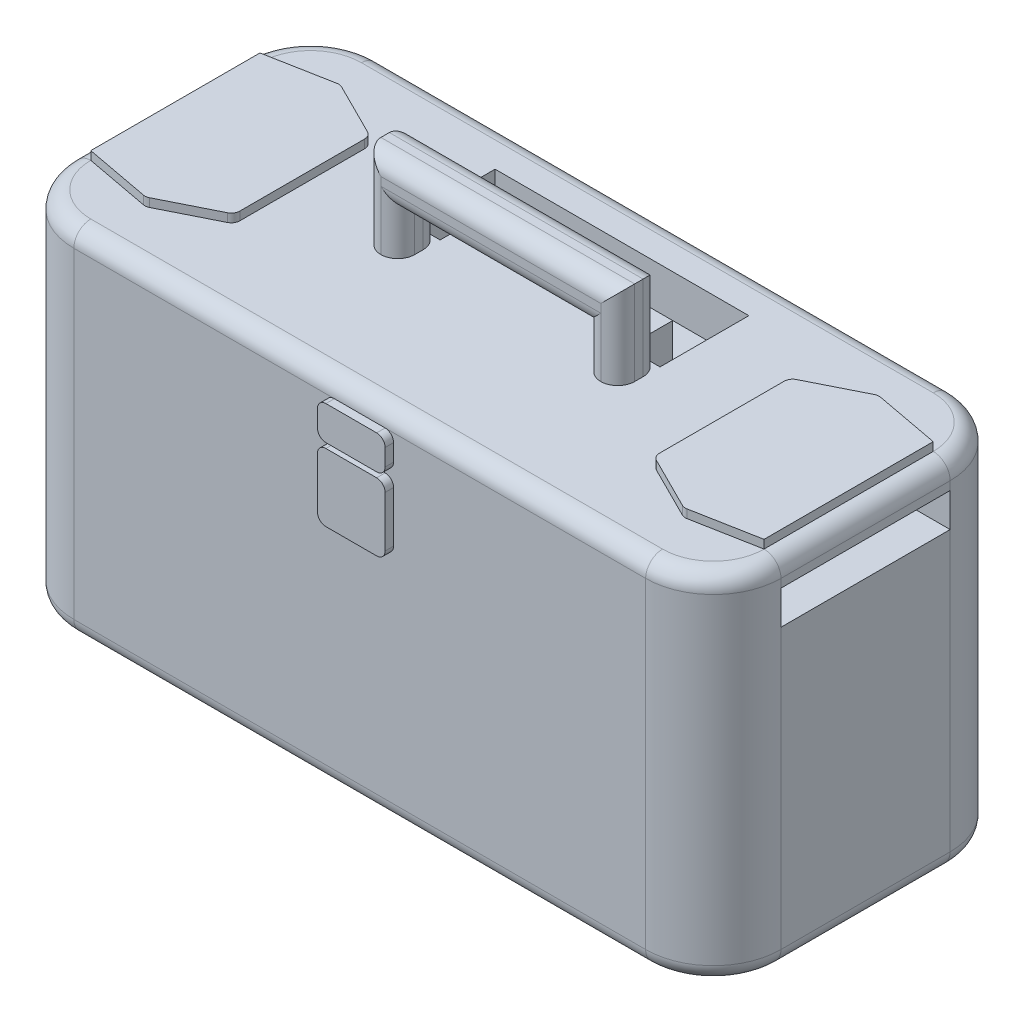
SolidWorks part; units mm, degrees
material "Kunststoff schwarz"
ref_plane "Vorne" through (0, 0, 0) normal (0, 0, 1) x (1, 0, 0)
ref_plane "Oben" through (0, 0, 0) normal (0, 1, 0) x (1, 0, 0)
ref_plane "Rechts" through (0, 0, 0) normal (1, 0, 0) x (0, 0, -1)
sketch "Skizze1" plane through (0, 0, 0) normal (0, 0, 1) x (1, 0, 0)
  line L1 (-209, 0) -> (209, 0)
  line L2 (-209, 0) -> (-209, 210)
  line L3 (-209, 210) -> (209, 210)
  line L4 (209, 0) -> (209, 210)
  point P4 (0, 0)
  dimension "D1" = 210
  dimension "D2" = 418
extrude "Aufsatz-Linear austragen1" add sketch "Skizze1" along normal mid plane 180
fillet "Verrundung1" radius 40 4 edges at (209, 105, 90) (209, 105, -90) (-209, 105, -90) (-209, 105, 90)
sketch "Skizze3" plane through (0, 210, 0) normal (0, 1, 0) x (1, 0, 0)
  line L0 (-75, -10) -> (-75, 65)
  line L1 (-75, 65) -> (75, 65)
  line L2 (75, 65) -> (75, -10)
  line L3 (75, -10) -> (55, -10)
  line L4 (55, -10) -> (55, 40)
  line L5 (55, 40) -> (-55, 40)
  line L6 (-55, 40) -> (-55, -10)
  line L7 (-55, -10) -> (-75, -10)
  line L8 (0, 90) -> (0, -90) construction
  line L9 (169, 90) -> (-169, 90) construction
  line L10 (169, -90) -> (-169, -90) construction
  dimension "D1" = 10
  dimension "D2" = 20
  dimension "D3" = 20
  dimension "D4" = 25
  dimension "D5" = 150
  dimension "D6" = 75
extrude "Schnitt-Linear austragen1" cut sketch "Skizze3" against normal blind 25
sketch "Skizze4" plane through (0, 0, 0) normal (0, 0, 1) x (1, 0, 0)
  line L0 (-75, 185) -> (-75, 260)
  line L1 (-75, 185) -> (-75, 210) construction
  line L2 (-75, 260) -> (75, 260)
  line L3 (75, 260) -> (75, 185)
  line L4 (-55, 185) -> (-55, 235)
  line L5 (-55, 235) -> (55, 235)
  line L6 (55, 235) -> (55, 185)
  line L7 (55, 185) -> (75, 185)
  line L8 (-75, 185) -> (-55, 185)
  dimension "D1" = 75
  dimension "D2" = 25
extrude "Aufsatz-Linear austragen2" add sketch "Skizze4" along normal mid plane 25
fillet "Verrundung2" radius 10 12 edges at (-75, 235, -12.5) (-55, 222.5, -12.5) (55, 222.5, -12.5) (0, 235, -12.5) (0, 260, -12.5) (75, 235, -12.5) (75, 235, 12.5) (55, 222.5, 12.5) (0, 260, 12.5) (0, 235, 12.5) (-55, 222.5, 12.5) (-75, 235, 12.5)
sketch "Skizze5" plane through (209, 0, 0) normal (1, 0, 0) x (0, 0, -1)
  line L0 (-50, 210) -> (-50, 0) construction
  line L1 (-50, 195) -> (50, 195)
  line L2 (-50, 195) -> (-50, 175)
  line L3 (-50, 175) -> (50, 175)
  line L4 (50, 195) -> (50, 175)
  line L5 (50, 0) -> (50, 210) construction
  line L6 (-50, 210) -> (50, 210) construction
  dimension "D1" = 15
  dimension "D2" = 20
extrude "Schnitt-Linear austragen2" cut sketch "Skizze5" against normal blind 20
sketch "Skizze6" plane through (-209, 0, 0) normal (-1, 0, 0) x (0, 0, 1)
  line L0 (-50, 210) -> (-50, 0) construction
  line L1 (-50, 195) -> (50, 195)
  line L2 (-50, 195) -> (-50, 175)
  line L3 (-50, 175) -> (50, 175)
  line L4 (50, 195) -> (50, 175)
  line L5 (50, 0) -> (50, 210) construction
  line L6 (50, 210) -> (-50, 210) construction
  dimension "D1" = 15
  dimension "D2" = 20
extrude "Schnitt-Linear austragen3" cut sketch "Skizze6" against normal blind 20
fillet "Verrundung4" radius 10 16 edges at (-209, 0, 0) (-197.2843, 0, 78.2843) (0, 0, 90) (197.2843, 0, 78.2843) (209, 0, 0) (197.2843, 0, -78.2843) (0, 0, -90) (197.2843, 210, -78.2843) (209, 210, 0) (197.2843, 210, 78.2843) (0, 210, 90) (-197.2843, 210, 78.2843) (-209, 210, 0) (-197.2843, 210, -78.2843) (-197.2843, 0, -78.2843) (0, 210, -90)
sketch "Skizze7" plane through (0, 210, 0) normal (0, 1, 0) x (1, 0, 0)
  line L0 (-199, 50) -> (-160.6531, 57.19)
  line L1 (-157.4956, 56.7478) -> (-126.7639, 41.382)
  line L2 (-124, 36.9098) -> (-124, -36.9098)
  line L3 (-126.7639, -41.382) -> (-157.4956, -56.7478)
  line L4 (-160.6531, -57.19) -> (-199, -50)
  line L5 (-209, 0) -> (0, 0) construction
  line L6 (-209, -50) -> (-209, 50) construction
  line L7 (-199, 50) -> (-199, -50)
  line L8 (0, 0) -> (0, 90) construction
  line L9 (-169, 90) -> (169, 90) construction
  line L10 (199, 50) -> (199, -50)
  line L11 (160.6531, -57.19) -> (199, -50)
  line L12 (126.7639, -41.382) -> (157.4956, -56.7478)
  line L13 (124, 36.9098) -> (124, -36.9098)
  line L14 (157.4956, 56.7478) -> (126.7639, 41.382)
  line L15 (199, 50) -> (160.6531, 57.19)
  arc A0 (-160.6531, -57.19) -> (-157.4956, -56.7478) centre (-159.7317, -52.2757) ccw
  arc A1 (-124, -36.9098) -> (-126.7639, -41.382) centre (-129, -36.9098) cw
  arc A2 (-124, 36.9098) -> (-126.7639, 41.382) centre (-129, 36.9098) ccw
  arc A3 (-157.4956, 56.7478) -> (-160.6531, 57.19) centre (-159.7317, 52.2757) ccw
  arc A4 (157.4956, 56.7478) -> (160.6531, 57.19) centre (159.7317, 52.2757) cw
  arc A5 (124, 36.9098) -> (126.7639, 41.382) centre (129, 36.9098) cw
  arc A6 (124, -36.9098) -> (126.7639, -41.382) centre (129, -36.9098) ccw
  arc A7 (160.6531, -57.19) -> (157.4956, -56.7478) centre (159.7317, -52.2757) cw
  point P18 (-159, -57.5)
  point P21 (-124, -40)
  point P24 (-124, 40)
  point P27 (-159, 57.5)
  point P42 (159, 57.5)
  point P43 (124, 40)
  point P44 (124, -40)
  point P45 (159, -57.5)
  dimension "D5" = 5
  dimension "D1" = 75
  dimension "D2" = 115
  dimension "D3" = 35
  dimension "D4" = 80
extrude "Aufsatz-Linear austragen3" add sketch "Skizze7" along normal blind 5
sketch "Skizze8" plane through (0, 0, 90) normal (0, 0, 1) x (1, 0, 0)
  line L0 (169, 200) -> (-169, 200) construction
  line L1 (-15, 200) -> (15, 200)
  line L2 (-20, 195) -> (-20, 185)
  line L3 (-15, 180) -> (15, 180)
  line L4 (20, 195) -> (20, 185)
  line L5 (0, 210) -> (0, 0) construction
  line L6 (-15, 177) -> (15, 177)
  line L7 (-20, 172) -> (-20, 142)
  line L8 (-15, 137) -> (15, 137)
  line L9 (20, 172) -> (20, 142)
  line L10 (-169, 210) -> (169, 210) construction
  line L11 (169, 0) -> (-169, 0) construction
  arc A0 (20, 172) -> (15, 177) centre (15, 172) ccw
  arc A1 (20, 142) -> (15, 137) centre (15, 142) cw
  arc A2 (-15, 137) -> (-20, 142) centre (-15, 142) cw
  arc A3 (-15, 177) -> (-20, 172) centre (-15, 172) ccw
  arc A4 (-20, 185) -> (-15, 180) centre (-15, 185) ccw
  arc A5 (15, 180) -> (20, 185) centre (15, 185) ccw
  arc A6 (20, 195) -> (15, 200) centre (15, 195) ccw
  arc A7 (-15, 200) -> (-20, 195) centre (-15, 195) ccw
  point P20 (20, 137)
  point P23 (-20, 137)
  point P26 (-20, 177)
  point P29 (-20, 180)
  point P36 (-20, 200)
  dimension "D5" = 5
  dimension "D1" = 40
  dimension "D2" = 40
  dimension "D3" = 3
  dimension "D4" = 20
extrude "Aufsatz-Linear austragen4" add sketch "Skizze8" along normal blind 5
